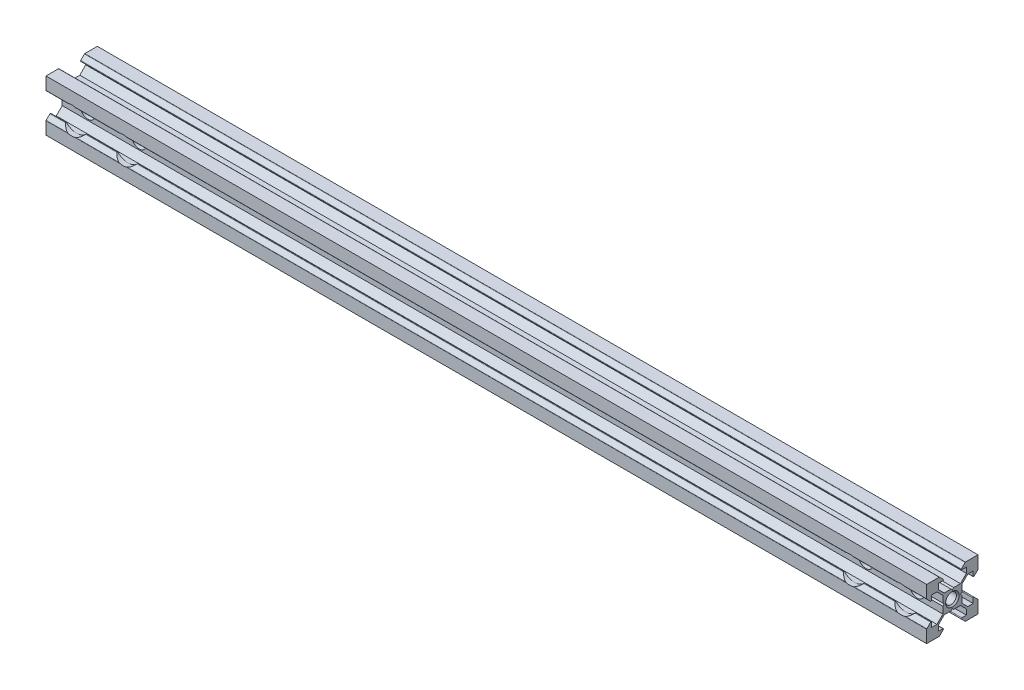
SolidWorks part; units mm, degrees
material "Alloy Steel"
ref_plane "Front Plane" through (0, 0, 0) normal (0, 0, 1) x (1, 0, 0)
ref_plane "Top Plane" through (0, 0, 0) normal (0, 1, 0) x (1, 0, 0)
ref_plane "Right Plane" through (0, 0, 0) normal (1, 0, 0) x (0, 0, -1)
sketch "Sketch2" plane through (0, 0, 0) normal (1, 0, 0) x (0, 0, -1)
  line L0 (0, 2) -> (0, 3) construction
  line L5 (0, 3) -> (-0.5, 3.5)
  line L6 (-0.5, 3.5) -> (-3.01, 3.5)
  line L7 (-3.01, 3.5) -> (-5.2091, 5.6991)
  line L8 (-5.2091, 5.6991) -> (-5.2091, 7.6991)
  line L9 (-5.2091, 7.6991) -> (-3.4791, 7.6991)
  line L10 (-3.4791, 7.6991) -> (-3.4791, 7.8991) construction
  line L11 (-3.4791, 7.8991) -> (-3.3377, 8.0405) construction
  line L12 (-3.3377, 8.0405) -> (-4.7378, 9.4406)
  line L13 (-4.7378, 9.4406) -> (-4.8792, 9.2992) construction
  line L14 (-4.8792, 9.2992) -> (-4.8792, 9.4992) construction
  line L15 (-4.8792, 9.4992) -> (-9.4992, 9.4992)
  line L16 (0, 0) -> (-11.6899, 11.6899) construction
  line L17 (0, 0) -> (-16.8134, 0) construction
  line L18 (-9.4992, 4.8792) -> (-9.4992, 9.4992)
  line L19 (-8.0405, 3.3377) -> (-9.4406, 4.7378)
  line L20 (-7.6991, 5.2091) -> (-7.6991, 3.4791)
  line L21 (-5.6991, 5.2091) -> (-7.6991, 5.2091)
  line L22 (-3.5, 3.01) -> (-5.6991, 5.2091)
  line L23 (-3.5, 0.5) -> (-3.5, 3.01)
  line L24 (-3, 0) -> (-3.5, 0.5)
  line L25 (3, 0) -> (3.5, 0.5)
  line L26 (3.5, 0.5) -> (3.5, 3.01)
  line L27 (3.5, 3.01) -> (5.6991, 5.2091)
  line L28 (5.6991, 5.2091) -> (7.6991, 5.2091)
  line L29 (7.6991, 5.2091) -> (7.6991, 3.4791)
  line L30 (8.0405, 3.3377) -> (9.4406, 4.7378)
  line L31 (9.4992, 4.8792) -> (9.4992, 9.4992)
  line L32 (4.8792, 9.4992) -> (9.4992, 9.4992)
  line L33 (3.3377, 8.0405) -> (4.7378, 9.4406)
  line L34 (5.2091, 7.6991) -> (3.4791, 7.6991)
  line L35 (5.2091, 5.6991) -> (5.2091, 7.6991)
  line L36 (3.01, 3.5) -> (5.2091, 5.6991)
  line L37 (0.5, 3.5) -> (3.01, 3.5)
  line L38 (0, 3) -> (0.5, 3.5)
  line L39 (2, 0) -> (3, 0) construction
  line L40 (7.6991, 3.4791) -> (7.8991, 3.4791) construction
  line L41 (7.8991, 3.4791) -> (8.0405, 3.3377) construction
  line L42 (9.4406, 4.7378) -> (9.2992, 4.8792) construction
  line L43 (9.2992, 4.8792) -> (9.4992, 4.8792) construction
  line L44 (0, 0) -> (11.6899, 11.6899) construction
  line L45 (0, 0) -> (0, 16.8134) construction
  line L46 (0, -3) -> (0.5, -3.5)
  line L47 (0.5, -3.5) -> (3.01, -3.5)
  line L48 (3.01, -3.5) -> (5.2091, -5.6991)
  line L49 (5.2091, -5.6991) -> (5.2091, -7.6991)
  line L50 (5.2091, -7.6991) -> (3.4791, -7.6991)
  line L51 (3.3377, -8.0405) -> (4.7378, -9.4406)
  line L52 (4.8792, -9.4992) -> (9.4992, -9.4992)
  line L53 (9.4992, -4.8792) -> (9.4992, -9.4992)
  line L54 (8.0405, -3.3377) -> (9.4406, -4.7378)
  line L55 (7.6991, -5.2091) -> (7.6991, -3.4791)
  line L56 (5.6991, -5.2091) -> (7.6991, -5.2091)
  line L57 (3.5, -3.01) -> (5.6991, -5.2091)
  line L58 (3.5, -0.5) -> (3.5, -3.01)
  line L59 (3, 0) -> (3.5, -0.5)
  line L60 (0, -2) -> (0, -3) construction
  line L61 (3.4791, -7.6991) -> (3.4791, -7.8991) construction
  line L62 (3.4791, -7.8991) -> (3.3377, -8.0405) construction
  line L63 (4.7378, -9.4406) -> (4.8792, -9.2992) construction
  line L64 (4.8792, -9.2992) -> (4.8792, -9.4992) construction
  line L65 (0, 0) -> (11.6899, -11.6899) construction
  line L66 (0, 0) -> (16.8134, 0) construction
  line L67 (-3, 0) -> (-3.5, -0.5)
  line L68 (-3.5, -0.5) -> (-3.5, -3.01)
  line L69 (-3.5, -3.01) -> (-5.6991, -5.2091)
  line L70 (-5.6991, -5.2091) -> (-7.6991, -5.2091)
  line L71 (-7.6991, -5.2091) -> (-7.6991, -3.4791)
  line L72 (-8.0405, -3.3377) -> (-9.4406, -4.7378)
  line L73 (-9.4992, -4.8792) -> (-9.4992, -9.4992)
  line L74 (-4.8792, -9.4992) -> (-9.4992, -9.4992)
  line L75 (-3.3377, -8.0405) -> (-4.7378, -9.4406)
  line L76 (-5.2091, -7.6991) -> (-3.4791, -7.6991)
  line L77 (-5.2091, -5.6991) -> (-5.2091, -7.6991)
  line L78 (-3.01, -3.5) -> (-5.2091, -5.6991)
  line L79 (-0.5, -3.5) -> (-3.01, -3.5)
  line L80 (0, -3) -> (-0.5, -3.5)
  line L81 (-2, 0) -> (-3, 0) construction
  line L82 (-7.6991, -3.4791) -> (-7.8991, -3.4791) construction
  line L83 (-7.8991, -3.4791) -> (-8.0405, -3.3377) construction
  line L84 (-9.4406, -4.7378) -> (-9.2992, -4.8792) construction
  line L85 (-9.2992, -4.8792) -> (-9.4992, -4.8792) construction
  line L86 (0, 0) -> (-11.6899, -11.6899) construction
  line L87 (0, 0) -> (0, -16.8134) construction
  circle A0 centre (0, 0) radius 2
  arc A1 (-3.3377, 8.0405) -> (-3.4791, 7.6991) centre (-3.4791, 7.8991) cw
  arc A2 (-4.7378, 9.4406) -> (-4.8792, 9.4992) centre (-4.8792, 9.2992) ccw
  arc A3 (-9.4406, 4.7378) -> (-9.4992, 4.8792) centre (-9.2992, 4.8792) cw
  arc A4 (-8.0405, 3.3377) -> (-7.6991, 3.4791) centre (-7.8991, 3.4791) ccw
  arc A5 (8.0405, 3.3377) -> (7.6991, 3.4791) centre (7.8991, 3.4791) cw
  arc A6 (9.4406, 4.7378) -> (9.4992, 4.8792) centre (9.2992, 4.8792) ccw
  arc A7 (4.7378, 9.4406) -> (4.8792, 9.4992) centre (4.8792, 9.2992) cw
  arc A8 (3.3377, 8.0405) -> (3.4791, 7.6991) centre (3.4791, 7.8991) ccw
  arc A9 (3.3377, -8.0405) -> (3.4791, -7.6991) centre (3.4791, -7.8991) cw
  arc A10 (4.7378, -9.4406) -> (4.8792, -9.4992) centre (4.8792, -9.2992) ccw
  arc A11 (9.4406, -4.7378) -> (9.4992, -4.8792) centre (9.2992, -4.8792) cw
  arc A12 (8.0405, -3.3377) -> (7.6991, -3.4791) centre (7.8991, -3.4791) ccw
  arc A13 (-8.0405, -3.3377) -> (-7.6991, -3.4791) centre (-7.8991, -3.4791) cw
  arc A14 (-9.4406, -4.7378) -> (-9.4992, -4.8792) centre (-9.2992, -4.8792) ccw
  arc A15 (-4.7378, -9.4406) -> (-4.8792, -9.4992) centre (-4.8792, -9.2992) cw
  arc A16 (-3.3377, -8.0405) -> (-3.4791, -7.6991) centre (-3.4791, -7.8991) ccw
  point P0 (0, 0)
  point P22 (0, 0)
  point P64 (0, 0)
  point P93 (0, 0)
  point P122 (0, 0)
  dimension "D1" = 4
  dimension "D13" = 0.2
  dimension "D18" = 0.2
  dimension "D2" = 1
  dimension "D3" = 0.5
  dimension "D4" = 135
  dimension "D5" = 2.51
  dimension "D6" = 135
  dimension "D7" = 3.11
  dimension "D8" = 2
  dimension "D9" = 1.73
  dimension "D10" = 0.2
  dimension "D11" = 0.2
  dimension "D12" = 135
  dimension "D14" = 1.98
  dimension "D15" = 90
  dimension "D16" = 0.2
  dimension "D17" = 0.2
  dimension "D19" = 4
  dimension "D20" = 45
extrude "Main Body" add sketch "Sketch2" along normal blind 163 and the other way blind 163 contours L75 A16 L76 L77 L78 L79 L80 L46 L47 L48 L49 L50 A9 L51 A10 L52 L53 A11 L54 A12 L55 L56 L57 L58 L59 L25 L26 L27 L28 L29 A5 L30 A6 L31 L32 A7 L33 A8 L34 L35 L36 L37 L38 L5 L6 L7 L8 L9 A1 L12 A2 region at (0, 3.06, -0.44)
chamfer "Chamfer1" distance 0.5 angle 45 1 edges at (163, 0, -2)
chamfer "Chamfer2" distance 0.5 angle 45 1 edges at (-163, 0, -2)
sketch "Sketch4" plane through (0, 0, 0) normal (0, 0, 1) x (1, 0, 0)
  line L0 (-163, 0) -> (163, 0) construction
  line L1 (-163, -3.3377) -> (-163, -4.7378) construction
  line L3 (0, 0) -> (0, -2.3395) construction
  line L4 (163, -0.5) -> (163, -3.01) construction
  circle A0 centre (-153.5, 0) radius 2.65
  circle A1 centre (-134.5, 0) radius 2.65
  circle A6 centre (153.5, 0) radius 2.65
  circle A7 centre (134.5, 0) radius 2.65
  dimension "D1" = 5.3
  dimension "D2" = 5.3
  dimension "D7" = 5.3
  dimension "D8" = 5.3
  dimension "D3" = 9.5
  dimension "D4" = 19
  dimension "D5" = 9.5
  dimension "D6" = 19
extrude "Cut-Extrude1" cut sketch "Sketch4" against normal through all both and the other way through all
sketch "Sketch5" plane through (0, 0, 9.4992) normal (0, 0, 1) x (1, 0, 0)
  circle A0 centre (-153.5, 0) radius 5
  circle A1 centre (-134.5, 0) radius 5
  circle A6 centre (134.5, 0) radius 5
  circle A7 centre (153.5, 0) radius 5
  dimension "D1" = 10
  dimension "D2" = 10
  dimension "D3" = 10
  dimension "D4" = 10
extrude "Cut-Extrude2" cut sketch "Sketch5" against normal up to surface (1.8001 mm away) and the other way through all up to face at (0, 4.3441, 7.6991)
